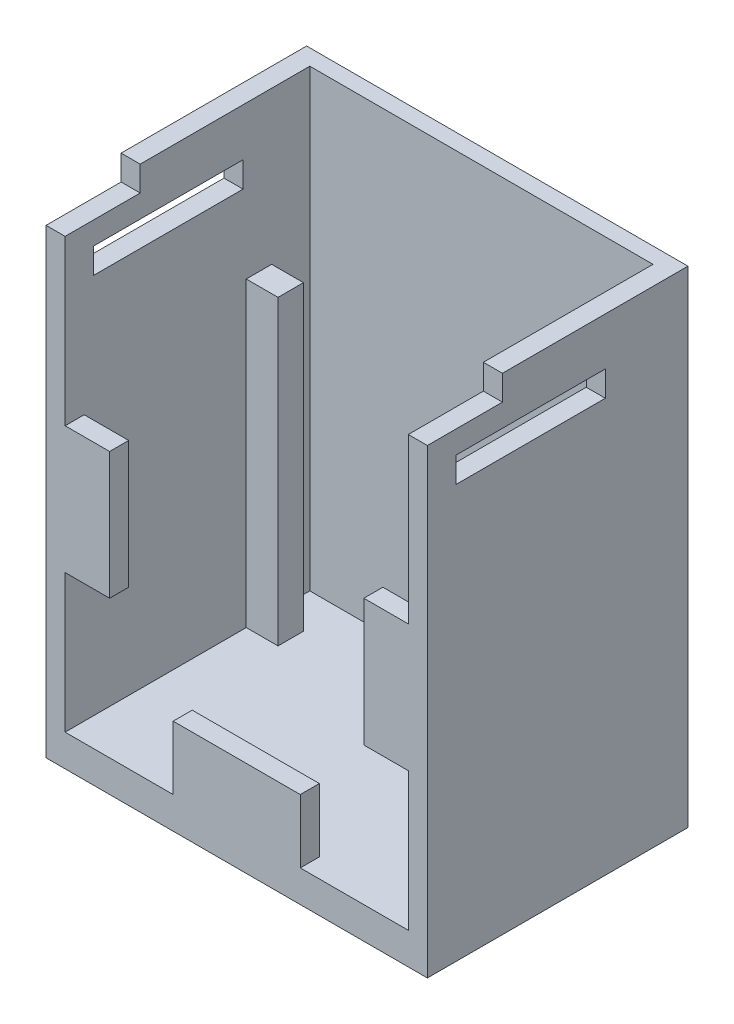
SolidWorks part; units mm, degrees
material "ABS"
ref_plane "Front Plane" through (0, 0, 0) normal (0, 0, 1) x (1, 0, 0)
ref_plane "Top Plane" through (0, 0, 0) normal (0, 1, 0) x (1, 0, 0)
ref_plane "Right Plane" through (0, 0, 0) normal (1, 0, 0) x (0, 0, -1)
sketch "Sketch1" plane through (0, 0, 0) normal (0, 0, 1) x (1, 0, 0)
  line L1 (15.24, -25.4) -> (-15.24, -25.4)
  line L2 (15.24, -25.4) -> (15.24, 15.24)
  line L3 (15.24, 15.24) -> (-15.24, 15.24)
  line L4 (-15.24, -25.4) -> (-15.24, 15.24)
  point P0 (0, 0)
  dimension "D1" = 30.48
  dimension "D2" = 40.64
extrude "Initial Block" add sketch "Sketch1" along normal blind 19.05 and the other way blind 1.778
sketch "Sketch2" plane through (0, 15.24, 0) normal (0, 1, 0) x (1, 0, 0)
  line L0 (15.24, 1.778) -> (-15.24, 1.778) construction
  line L1 (-13.716, 0.508) -> (13.716, 0.508)
  line L2 (-13.716, 0.508) -> (-13.716, -19.05)
  line L3 (-13.716, -19.05) -> (13.716, -19.05)
  line L4 (13.716, 0.508) -> (13.716, -19.05)
  line L5 (0, 1.778) -> (0, -14.7779) construction
  line L6 (15.24, -19.05) -> (-15.24, -19.05) construction
  point P9 (0, 1.778)
  point P11 (0, 0.508)
  point P12 (0, 0.508)
  dimension "D1" = 27.432
  dimension "D2" = 1.27
  dimension "D3" = 0
extrude "Initial Cut" cut sketch "Sketch2" against normal blind 38.1
ref_plane "Plane1" through (0, 0, 19.05) normal (0, 0, 1) x (1, 0, 0)
ref_plane "Plane2" through (0, 0, 0) normal (1, 0, 0) x (0, 0, -1)
sketch "Sketch20" plane through (0, 0, 19.05) normal (0, 0, 1) x (1, 0, 0)
  line L0 (-15.24, 9.398) -> (-15.24, -22.86) construction
  line L1 (-15.24, -22.86) -> (15.24, -22.86) construction
  line L2 (15.24, -22.86) -> (15.24, 9.398) construction
  line L3 (-15.24, -6.731) -> (15.24, -6.731) construction
  line L4 (15.24, 9.398) -> (-15.24, 9.398) construction
  line L5 (-15.24, -11.811) -> (-10.16, -11.811)
  line L6 (-15.24, -11.811) -> (-15.24, -1.651)
  line L7 (-15.24, -1.651) -> (-10.16, -1.651)
  line L8 (-10.16, -11.811) -> (-10.16, -1.651)
  line L9 (0, 9.398) -> (0, -22.86) construction
  line L10 (15.24, -11.811) -> (15.24, -1.651)
  line L11 (-5.08, -17.78) -> (5.08, -17.78)
  line L12 (-5.08, -17.78) -> (-5.08, -22.86)
  line L13 (-5.08, -22.86) -> (5.08, -22.86)
  line L14 (5.08, -17.78) -> (5.08, -22.86)
  line L15 (15.24, -11.811) -> (10.16, -11.811)
  line L16 (10.16, -11.811) -> (10.16, -1.651)
  line L17 (15.24, -1.651) -> (10.16, -1.651)
  line L19 (-13.716, -22.86) -> (13.716, -22.86) construction
  line L23 (-15.24, 15.24) -> (-15.24, -25.4) construction
  line L24 (15.24, -25.4) -> (15.24, 15.24) construction
  dimension "D1" = 10.16
  dimension "D2" = 5.08
  dimension "D3" = 10.16
  dimension "D4" = 5.08
  dimension "D5" = 5.08
  dimension "D6" = 10.16
extrude "Boss-Extrude1" add sketch "Sketch20" against normal blind 1.524
sketch "Sketch21" plane through (-13.716, 0, 0) normal (1, 0, 0) x (0, 0, -1)
  line L0 (-19.05, -1.651) -> (-19.05, 15.24) construction
  line L1 (-4.572, 1.27) -> (-2.54, 1.27)
  line L2 (-4.572, 1.27) -> (-4.572, -22.86)
  line L3 (-4.572, -22.86) -> (-2.54, -22.86)
  line L4 (-2.54, 1.27) -> (-2.54, -22.86)
  line L5 (0.508, 15.24) -> (-19.05, 15.24) construction
  line L6 (0.508, -22.86) -> (-19.05, -22.86) construction
  dimension "D1" = 2.032
  dimension "D2" = 14.478
  dimension "D3" = 13.97
  dimension "D4" = 0
extrude "Boss-Extrude2" add sketch "Sketch21" along normal blind 2.54 contours L4 L3 L2 L1
mirror "Mirror2" about plane through (0, 0, 0) normal (1, 0, 0) of "Boss-Extrude2"
sketch "Sketch27" plane through (15.24, 0, 0) normal (1, 0, 0) x (0, 0, -1)
  line L0 (-16.764, 9.652) -> (-4.826, 9.652)
  line L1 (-16.764, 9.652) -> (-16.764, 7.62)
  line L2 (-16.764, 7.62) -> (-4.826, 7.62)
  line L3 (-4.826, 9.652) -> (-4.826, 7.62)
  line L5 (-19.05, -25.4) -> (-19.05, 15.24) construction
  line L7 (1.778, -25.4) -> (-19.05, -25.4) construction
  dimension "D1" = 11.938
  dimension "D2" = 2.032
  dimension "D3" = 33.02
  dimension "D4" = 2.286
extrude "Cut-Extrude6" cut sketch "Sketch27" against normal up to next
mirror "Mirror6" about plane through (0, 0, 0) normal (1, 0, 0) of "Cut-Extrude6"
sketch "Sketch28" plane through (0, 0, 19.05) normal (0, 0, 1) x (1, 0, 0)
  line L0 (15.24, -25.4) -> (15.24, 15.24) construction
  line L1 (-15.24, 15.24) -> (15.24, 15.24)
  line L2 (-15.24, 15.24) -> (-15.24, 13.462)
  line L3 (-15.24, 13.462) -> (15.24, 13.462)
  line L4 (15.24, 15.24) -> (15.24, 13.462)
  dimension "D1" = 1.778
extrude "Cut-Extrude7" cut sketch "Sketch28" against normal through all
sketch "Sketch29" plane through (0, 0, 19.05) normal (0, 0, 1) x (1, 0, 0)
  line L0 (15.24, -25.4) -> (15.24, 13.462) construction
  line L1 (-15.24, 13.462) -> (15.24, 13.462)
  line L2 (-15.24, 13.462) -> (-15.24, 11.462)
  line L3 (-15.24, 11.462) -> (15.24, 11.462)
  line L4 (15.24, 13.462) -> (15.24, 11.462)
  dimension "D1" = 2
extrude "Cut-Extrude8" cut sketch "Sketch29" against normal blind 6
